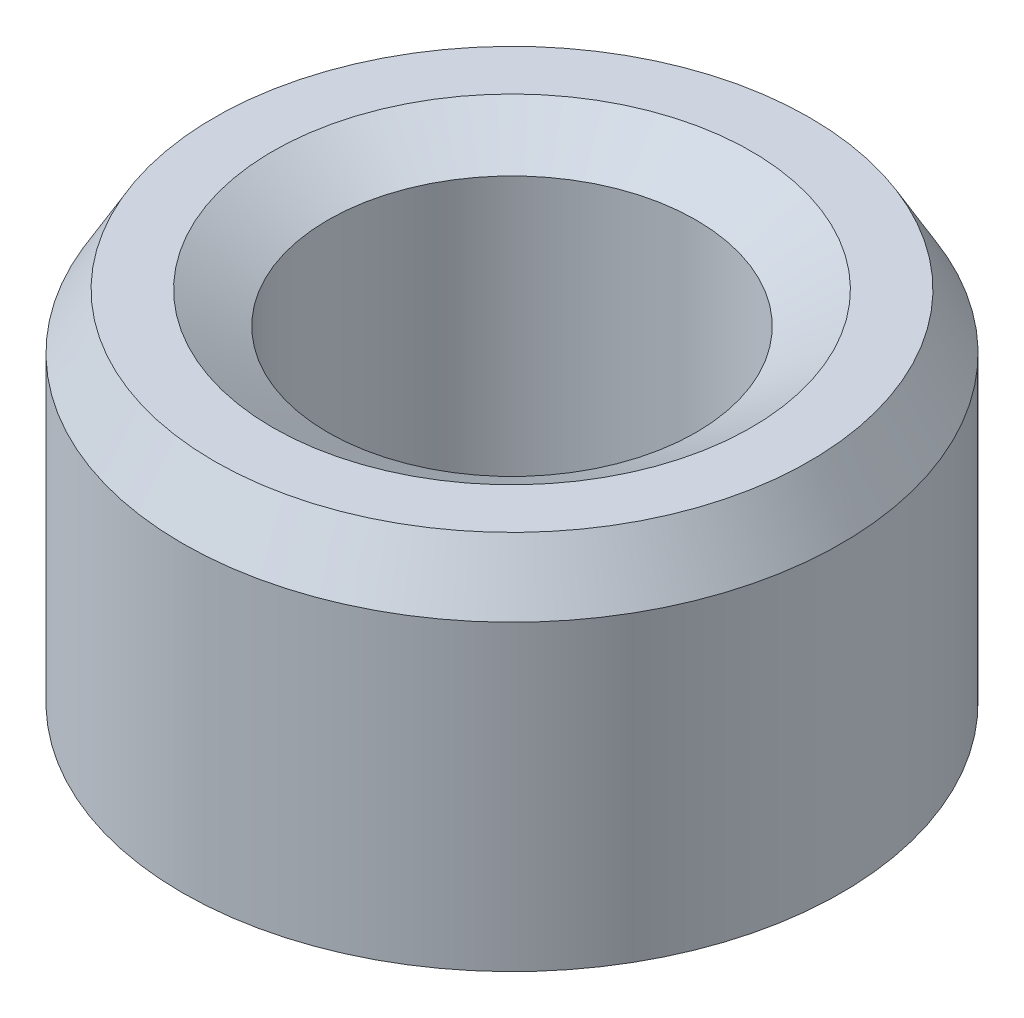
SolidWorks part; units mm, degrees
ref_plane "Front Plane" through (0, 0, 0) normal (0, 0, 1) x (1, 0, 0)
ref_plane "Top Plane" through (0, 0, 0) normal (0, 1, 0) x (1, 0, 0)
ref_plane "Right Plane" through (0, 0, 0) normal (1, 0, 0) x (0, 0, -1)
sketch "Sketch1" plane through (0, 0, 0) normal (0, 1, 0) x (1, 0, 0)
  circle A0 centre (0, 0) radius 17.5
  dimension "SLEEVE_OD" = 35
extrude "Boss-Extrude1" add sketch "Sketch1" along normal blind 20.6949
sketch "Sketch2" plane through (0, 0, 0) normal (0, 1, 0) x (1, 0, 0)
  circle A0 centre (0, 0) radius 9.7738
  dimension "BORE_D" = 19.5476
extrude "Cut-Extrude1" cut sketch "Sketch2" along normal through all
chamfer "Chamfer1" distance 2.9338 angle 30 4 edges at (0, 20.6949, 9.7738) (0, 0, 9.7738) (0, 0, 17.5) (0, 20.6949, 17.5) first distance on face at (0, 20.6949, 9.7738) first distance on face at (0, 0, 9.7738) first distance on face at (0, 20.6949, 17.5)
